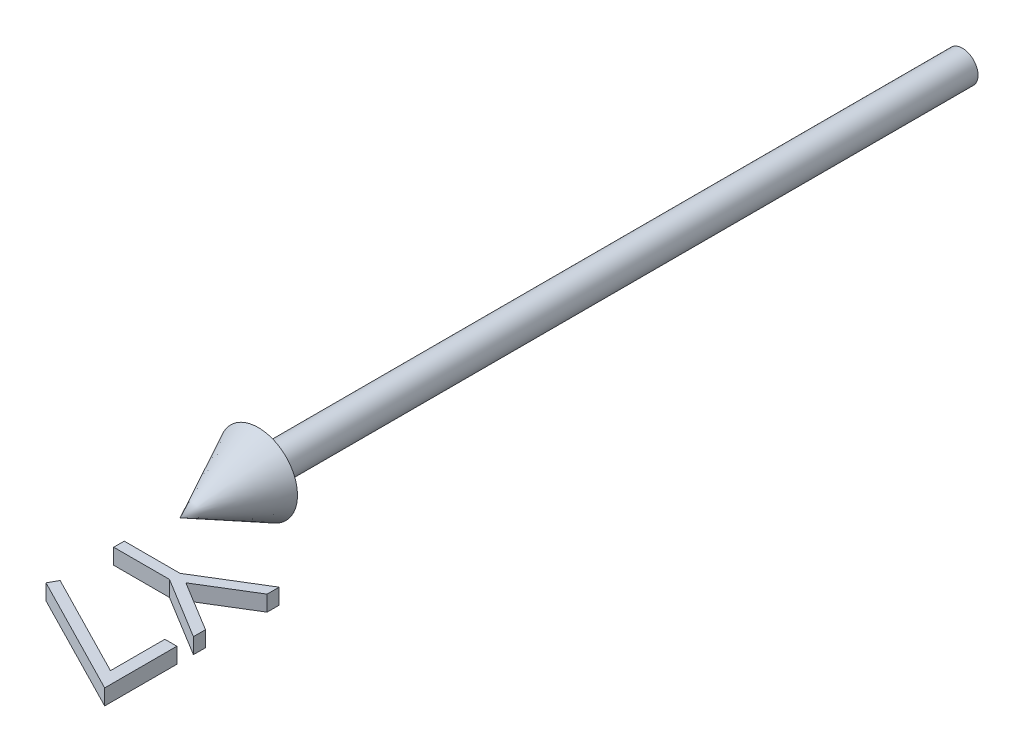
SolidWorks part; units mm, degrees
ref_plane "Front Plane" through (0, 0, 0) normal (0, 0, 1) x (1, 0, 0)
ref_plane "Top Plane" through (0, 0, 0) normal (0, 1, 0) x (1, 0, 0)
ref_plane "Right Plane" through (0, 0, 0) normal (1, 0, 0) x (0, 0, -1)
sketch "Sketch2" plane through (0, 0, 0) normal (0, 1, 0) x (1, 0, 0)
  line L0 (0, 41.95) -> (0, -114.4521) construction
  line L1 (-36.8894, 0) -> (41.4965, 0) construction
  line L2 (0, -100) -> (5, -90)
  line L3 (5, -90) -> (2, -90)
  line L4 (2, -90) -> (2, 0)
  line L5 (2, 0) -> (0, 0)
  line L6 (0, 0) -> (0, -100)
  dimension "D1" = 100
  dimension "D2" = 2
  dimension "D3" = 10
  dimension "D4" = 5
revolve "Revolve1" add sketch "Sketch2" angle 360 about L0
sketch "Sketch3" plane through (0, 0, 0) normal (0, 1, 0) x (1, 0, 0)
  line L0 (0, -101.5706) -> (0, -127.8138) construction
  text T0 "Y7\r\n\r\n\r\n" font "Century Gothic" height 15
extrude "Boss-Extrude1" add sketch "Sketch3" against normal blind 1 and the other way blind 1 separate body
equation "\"frame_arrow_length\"=100"
equation "\"D1@Sketch2\"=\"frame_arrow_length\""
equation "\"frame_arrow_odA\"=4"
equation "\"D2@Sketch2\"=\"frame_arrow_odA\"/2"
equation "\"frame_arrow_head_od\"=5"
equation "\"D4@Sketch2\"=\"frame_arrow_head_od\""
equation "\"frame_arrow_head_length\"=10"
equation "\"D3@Sketch2\"=\"frame_arrow_head_length\""
equation "\"tvarobot_theta1\"=30"
equation "\"link0_ringA_odA\"= 40"
equation "\"link0_ringA_odB\"= 25"
equation "\"link0_ringA_id\"= 20"
equation "\"link0_ringA_thickness\"= (\"link0_ringA_odB\" - \"link0_ringA_id\")/2"
equation "\"link0_ringA_height\"= 3"
equation "\"link0_ringA_heightA\"= 1.5"
equation "\"link0_ringA_heightB\"=\"link0_ringA_height\"-\"link0_ringA_heightA\""
equation "\"link0_ringB_odA\"= 40"
equation "\"link0_ringB_odB\"= 29"
equation "\"link0_ringB_id\"= \"link0_shaftA_bearing_id\"+1"
equation "\"link0_ringB_thickness\"= (\"link0_ringB_odB\" - \"link0_ringB_id\")/2"
equation "\"link0_ringB_height\"= 3"
equation "\"link0_ringB_heightA\"= 1.5"
equation "\"link0_ringB_heightB\"=\"link0_ringB_height\"-\"link0_ringB_heightA\""
equation "\"link0_shaftA_bearing_od\"=27"
equation "\"link0_shaftA_bearing_id\"=20"
equation "\"link0_shaftA_thrust_bearing_od\"=35"
equation "\"link0_shaftA_thrust_bearing_id\"=20.04"
equation "\"link0_shaftA_retaining_ring_id\"=18.5"
equation "\"link0_shaftA_retaining_ring_groove_width\"=1.5"
equation "\"link0_shaftA_spline_length\"=8.0"
equation "\"link0_shaftA_spline_depth\"=1.0"
equation "\"link0_shaftA_spline_width\"=4.0"
equation "\"link0_shaftA_odA\"=\"link0_shaftA_bearing_id\""
equation "\"link0_shaftA_odB\"=35"
equation "\"link0_shaftA_odC\"=\"link0_shaftA_bearing_id\""
equation "\"link0_shaftA_odD\"=\"link0_shaftA_odC\"-2*\"link0_shaftA_spline_depth\""
equation "\"link0_shaftA_odE\"=\"link0_shaftA_bearing_id\""
equation "\"link0_shaftA_odF\"=\"link0_shaftA_odE\"-2*\"link0_shaftA_spline_depth\""
equation "\"link0_shaftA_idA\"=10"
equation "\"link0_shaftA_idB\"=6"
equation "\"link0_shaftA_length\"=39.5"
equation "\"link0_shaftA_lengthA\"=8.0"
equation "\"link0_shaftA_lengthB\"=12.0"
equation "\"link0_shaftA_lengthC\"=35.0"
equation "\"link0_shaftA_lengthD\"=39.0"
equation "\"link0_shaftA_lengthE\"=\"link0_shaftA_length\"-\"link0_shaftA_lengthD\""
equation "\"link0_shaftA_offsetX\"=11"
equation "\"link0_shaftA_offsetY\"=0"
equation "\"link0_shaftA_bolt_pattern_dia\"=14"
equation "\"link0_motor_center_dist\"=26"
equation "\"link0_46t_pulley_spline_length\"=8"
equation "\"link0_46t_pulley_spline_depth\"=\"link0_shaftA_spline_depth\"*1.025"
equation "\"link0_46t_pulley_spline_width\"=\"link0_shaftA_spline_width\"*1.05"
equation "\"link0_46t_pulley_idA\"=\"link0_shaftA_bearing_id\"*1.025"
equation "\"link0_46t_pulley_idB\"=\"link0_46t_pulley_idA\"-2*\"link0_46t_pulley_spline_depth\""
equation "\"link0_shaftB_spline_length\"=10"
equation "\"link0_shaftB_spline_depth\"=1.0"
equation "\"link0_shaftB_spline_width\"=1.25"
equation "\"link0_shaftB_length\"=7"
equation "\"link0_shaftB_lengthA\"=1.5"
equation "\"link0_shaftB_lengthB\"=2.75"
equation "\"link0_shaftB_odA\"=32"
equation "\"link0_shaftB_odB\"=22"
equation "\"link0_shaftB_odC\"=20"
equation "\"link0_shaftB_idA\"=10"
equation "\"link0_shaftB_bolt_diameter\"=19"
equation "\"link0_shaftB_bearing_od\"=27"
equation "\"link0_shaftB_bearing_id\"=20"
equation "\"link0_motor_length\"=46.5"
equation "\"link0_motor_width\"=28.5"
equation "\"link0_motor_height\"=34"
equation "\"link0_motor_offset\"=8"
equation "\"link0_shellA_thickness\"=2.5"
equation "\"link0_shellB_thickness\"=\"link0_shellA_thickness\""
equation "\"link0_plateA_shellA_height\"=48"
equation "\"link0_shellA_width\" =\"link0_plateA_width\""
equation "\"link0_shellA_height\" = \"link0_plateA_shellA_height\"-\"link0_plateA_height\""
equation "\"link0_shellA_length\" = \"link0_plateA_lengthB\" "
equation "\"link0_shellB_length\"=\"link0_shellA_length\""
equation "\"link0_shellA_radius\" = 0.375*25.4"
equation "\"link0_shellA_radiusA\"= \"link0_plateA_radiusA\""
equation "\"link0_shellA_radiusB\"= \"link0_plateA_radiusB\""
equation "\"link0_shellA_radiusC\"= 3"
equation "\"link0_postA_height\"=7"
equation "\"link0_postA_width\"=16"
equation "\"link0_postA_length\"=20"
equation "\"link0_postA_posX\"=22"
equation "\"link0_postA_posY\"=17.5"
equation "\"link0_postA_pocket_width\"=6.0"
equation "\"link0_postA_pocket_length\"=2.5"
equation "\"link0_postA_pocket_depth\"=9"
equation "\"link0_postA_pocket_posZ\"=10"
equation "\"link0_postB_height\"=7"
equation "\"link0_postB_width\"=16"
equation "\"link0_postB_length\"=20"
equation "\"link0_postB_posX\"=22"
equation "\"link0_postB_posY\"=17.5"
equation "\"link0_postB_id\"=3.0"
equation "\"link0_postB_pocket_width\"=6.0"
equation "\"link0_postB_pocket_length\"=2.5"
equation "\"link0_postB_pocket_depth\"=9"
equation "\"link0_postB_pocket_posZ\"=10"
equation "\"link0_postC_height\"=7"
equation "\"link0_postC_width\"=16"
equation "\"link0_postC_length\"=20"
equation "\"link0_postC_posX\"=22"
equation "\"link0_postC_posY\"=17.5"
equation "\"link0_postC_id\"=3.0"
equation "\"link0_postC_pocket_width\"=6.0"
equation "\"link0_postC_pocket_length\"=2.5"
equation "\"link0_postC_pocket_depth\"=9"
equation "\"link0_postC_pocket_posZ\"=10"
equation "\"link0_postD_height\"=7"
equation "\"link0_postD_width\"=16"
equation "\"link0_postD_length\"=20"
equation "\"link0_postD_posX\"=22"
equation "\"link0_postD_posY\"=17.5"
equation "\"link0_postD_id\"=3.0"
equation "\"link0_postD_pocket_width\"=6.0"
equation "\"link0_postD_pocket_length\"=3.0"
equation "\"link0_postD_pocket_depth\"=9"
equation "\"link0_postD_pocket_posZ\"=10"
equation "\"link0_postE_height\"=5"
equation "\"link0_postE_width\"=16"
equation "\"link0_postE_length\"=\"link0_plateE_lengthA\"-\"link0_lip_height\""
equation "\"link0_postE_posZ\"=22"
equation "\"link0_postE_posX\"=17.5"
equation "\"link0_postE_posY\"=22"
equation "\"link0_postE_id\"=3.0"
equation "\"link0_postE_cbore_id\"=6.5"
equation "\"link0_postE_hole_id\"=3"
equation "\"link0_postF_posZ\"=22"
equation "\"link0_postF_posX\"=17.5"
equation "\"link0_postF_posY\"=\"link0_plateB_lengthA\"+4"
equation "\"link0_postF_id\"=3.0"
equation "\"link0_postF_cbore_id\"=6.5"
equation "\"link0_postF_hole_id\"=3"
equation "\"link0_postG_posZ\"=22"
equation "\"link0_postG_posX\"=17.5"
equation "\"link0_postG_posY\"=\"link0_plateB_lengthA\"+12"
equation "\"link0_postG_id\"=3.0"
equation "\"link0_postG_cbore_id\"=6.5"
equation "\"link0_postG_hole_id\"=3"
equation "\"link0_postHIJ_posY\"=6"
equation "\"link0_postH_posX\"=28"
equation "\"link0_postH_posY\"=20"
equation "\"link0_postH_posZ\"=20"
equation "\"link0_postH_length\"=10"
equation "\"link0_postI_posX\"=28"
equation "\"link0_postI_posY\"=20"
equation "\"link0_postI_posZ\"=135"
equation "\"link0_postI_length\"=10"
equation "\"link0_postJ_posX\"=28"
equation "\"link0_postJ_posY\"=20"
equation "\"link0_postJ_posZ\"=175"
equation "\"link0_postJ_length\"=10"
equation "\"link0_postK_posX\"=28"
equation "\"link0_postK_posY\"=20"
equation "\"link0_postK_posZ\"=175"
equation "\"link0_postK_length\"=10"
equation "\"link0_postL_posX\"=28"
equation "\"link0_postL_posY\"=20"
equation "\"link0_postL_posZ\"=135"
equation "\"link0_postL_length\"=10"
equation "\"link0_postM_posX\"=28"
equation "\"link0_postM_posY\"=20"
equation "\"link0_postM_posZ\"=35"
equation "\"link0_postM_length\"=10"
equation "\"link0_plateA_lengthA\"=30"
equation "\"link0_plateA_lengthB\"=150"
equation "\"link0_plateA_lengthC\"=30"
equation "\"link0_plateA_length\"=\"link0_plateA_lengthA\"+\"link0_plateA_lengthB\"+\"link0_plateA_lengthC\""
equation "\"link0_plateA_width\"=  68"
equation "\"link0_plateA_height\"= \"link0_plateA_radiusA\""
equation "\"link0_plateA_thickness\"=\"link0_shellA_thickness\""
equation "\"link0_plateA_radius\"= 9.5"
equation "\"link0_plateA_radiusA\"= 18"
equation "\"link0_plateA_radiusB\"= 18"
equation "\"link0_plateA_radiusC\"= 3"
equation "\"link0_plateB_length\"= 40"
equation "\"link0_plateB_width\"= \"link0_plateA_width\"*1.005"
equation "\"link0_plateB_height\"= \"link0_plateA_shellA_height\"*1.005"
equation "\"link0_plateB_lengthA\"=\"link0_lip_height\"+\"link0_plateD_thickness\"+\"link0_motor_mount_thickness\""
equation "\"link0_plateB_lengthB\"=\"link0_plateB_height\"-\"link0_plateB_lengthA\""
equation "\"link0_plateB_radiusA\"= \"link0_plateA_radiusA\""
equation "\"link0_plateB_radiusB\"= \"link0_plateA_radiusB\""
equation "\"link0_plateB_radiusC\"= 3"
equation "\"link0_plateB_idA\"=\"link0_shaftA_odC\"+1"
equation "\"link0_plateB_idB\"=\"link0_shaftA_bearing_od\"-2"
equation "\"link0_plateB_idC\"=\"link0_shaftA_bearing_od\"*1.005"
equation "\"link0_plateB_idD\"=\"link0_shaftA_thrust_bearing_od\"+1 "
equation "\"link0_plateB_depthA\"=1.0"
equation "\"link0_plateB_depthB\"=2.0"
equation "\"link0_plateB_depthC\"=8"
equation "\"link0_plateB_depthD\"=\"link0_plateB_length\"-\"link0_lip_height\"-\"link0_plateD_thickness\" "
equation "\"link0_plateC_length\"=\"link0_plateB_length\""
equation "\"link0_plateC_width\"= \"link0_plateB_width\""
equation "\"link0_plateC_height\"= .1*25.4"
equation "\"link0_plateA_hole_od\" = 0.1*25.4"
equation "\"link0_plateA_hole_delx\" = 0.5*25.4"
equation "\"link0_plateA_hole_delz\" = 0.75*25.4"
equation "\"link0_plateA_hole_offx\" = 0.0*25.4"
equation "\"link0_plateA_hole_offz\" = \"link0_plateA_length\"/2"
equation "\"link0_plateB_hole_od\" = 0.1*25.4"
equation "\"link0_plateB_hole_delx\"= 0.75*25.4"
equation "\"link0_plateB_hole_delz\"= 0.75*25.4"
equation "\"link0_plateB_hole_offx\"= 0.0*25.4"
equation "\"link0_plateB_hole_offz\"= 0.0*25.4"
equation "\"link0_plateC_hole_od\"= 0.1*25.4"
equation "\"link0_plateC_hole_delx\"= 0.75*25.4"
equation "\"link0_plateC_hole_delz\"= 0.75*25.4"
equation "\"link0_plateC_hole_offx\"= 0.0*25.4"
equation "\"link0_plateC_hole_offz\"= 0.0*25.4"
equation "\"link0_plateD_height\"=\"link0_plateB_height\"-2*\"link0_shellA_thickness\""
equation "\"link0_plateD_width\"=\"link0_plateB_width\"-2*\"link0_shellA_thickness\""
equation "\"link0_plateD_thickness\"=10"
equation "\"link0_plateD_radiusA\"=\"link0_plateB_radiusA\"-\"link0_shellA_thickness\""
equation "\"link0_plateD_odA\"= .375*25.4"
equation "\"link0_plateD_odB\"= .375*25.4"
equation "\"link0_plateD_bearing_id\"=20"
equation "\"link0_plateD_bearing_od\"=27"
equation "\"link0_plateE_radiusA\"=\"link0_plateA_radiusA\""
equation "\"link0_plateE_radiusB\"=\"link0_plateA_radiusB\""
equation "\"link0_plateE_radiusC\"=8.0"
equation "\"link0_plateE_length\"=30"
equation "\"link0_plateE_lengthA\"=16"
equation "\"link0_plateE_height\"=\"link0_plateB_height\""
equation "\"link0_plateE_width\"=\"link0_plateB_width\""
equation "\"link0_plateE_odA\"=\"gantry_coupler_id\"*0.99"
equation "\"link0_plateE_idA\"=\"link0_plateE_odA\"-20.0"
equation "\"link0_plateE_spline_depth\"=\"link0_poleA_spline_depth\"*1.05"
equation "\"link0_plateE_spline_width\"=\"link0_poleA_spline_width\"*1.075"
equation "\"link0_plateE_spline_length\"=\"link0_poleA_spline_length\""
equation "\"link0_plateE_coupler_length\"=46"
equation "\"link0_lip_height\"=5.0"
equation "\"link0_lip_thickness\"=2.0"
equation "\"link0_motor_mount_thickness\"=8.0"
equation "\"link0_motor_mount_idA\"=22"
equation "\"link0_motor_mount_idB\"=\"link0_shaftB_bearing_od\"*1.005"
equation "\"link0_motor_mount_idC\"=\"link0_shaftB_bearing_od\"-2"
equation "\"link0_motor_mount_depthA\"=5.5"
equation "\"link0_motor_mount_height\"=\"link0_plateD_height\""
equation "\"link0_motor_mount_width\"=\"link0_plateD_width\""
equation "\"link0_motor_mountL_height\"=36"
equation "\"link0_motor_mountL_heightA\"=12"
equation "\"link0_motor_mountL_length\"=50"
equation "\"link0_motor_mountL_lengthA\"=36"
equation "\"gantry_coupler_od\"=25.4*2.0"
equation "\"gantry_coupler_id\"=1.645*25.4"
equation "\"gantry_coupler_offsetX\"=\"link0_plateE_width\"/2"
equation "\"link0_poleA_odA\"=20"
equation "\"link0_poleA_odB\"=36"
equation "\"link0_poleA_idA\"=\"link0_poleA_odA\"-2*\"link0_poleA_thickness\""
equation "\"link0_poleA_idB\"=(\"link0_plateE_idA\"/2+1.5*\"link0_lip_thickness\")*1.04"
equation "\"link0_poleA_thickness\"=3.5"
equation "\"link0_poleA_length\"=100"
equation "\"link0_poleA_lengthA\"=18.5"
equation "\"link0_poleA_lengthB\"=80"
equation "\"link0_poleA_gasket_thickness\"=1.5"
equation "\"link0_poleA_spline_depth\"=1.0"
equation "\"link0_poleA_spline_width\"=4.0"
equation "\"link0_poleA_spline_length\"=10.0"
equation "\"link1_plateB_length\"=30"
equation "\"link1_lip_height\"=\"link0_lip_height\""
equation "\"link0_tension_plateA_width\"=12"
equation "\"link0_tension_plateA_lengthA\"=10.5"
equation "\"link0_tension_plateB_width\"=\"link0_tension_plateA_width\""
equation "\"link0_tension_plateB_lengthA\"=\"link0_tension_plateA_lengthA\""
equation "\"link0_tension_wheelA_posZ\"=7"
equation "\"link0_tension_wheelA_posX\"=\"link0_plateD_height\"/2-\"link0_tension_plateA_lengthA\""
equation "\"link0_m2_clear_hole_id\"=2.35"
equation "\"link0_m2_insert_hole_id\"=2.5"
equation "\"link0_m2_tap_hole_id\"=1.75"
equation "\"link0_m2_nut_socket_width\"=4.25"
equation "\"link0_m2_nut_socket_depth\"=2.5"
equation "\"link0_m2_cbore_id\"=3.75"
equation "\"link0_m2_cbore_depth\"=7"
equation "\"link0_m2_5_clear_hole_id\"=2.75"
equation "\"link0_m2_5_insert_hole_id\"=2.75"
equation "\"link0_m2_5_tap_hole_id\"=2.25"
equation "\"link0_m2_5_nut_socket_width\"=5.25"
equation "\"link0_m2_5_nut_socket_depth\"=2.5"
equation "\"link0_m2_5_cbore_id\"=4.75"
equation "\"link0_m2_5_cbore_depth\"=2.5"
equation "\"link0_m2_5_insert_access_length\"=6.0"
equation "\"link0_m2_5_insert_access_width\"=3.0"
equation "\"link0_m3_clear_hole_id\"=3.25"
equation "\"link0_m3_insert_hole_id\"=3"
equation "\"link0_m3_tap_hole_id\"=2.75"
equation "\"link0_m3_nut_socket_width\"=5.75"
equation "\"link0_m3_nut_socket_depth\"=4.0"
equation "\"link0_m3_cbore_id\"=5.75"
equation "\"link0_m3_cbore_depth\"=3.5"
equation "\"link0_m3_insert_access_length\"=4.5"
equation "\"link0_m3_insert_access_width\"=3.5"
equation "\"link0_rpi_mount_height\"=6"
equation "\"link0_rpi_mount_width\"=49"
equation "\"link0_rpi_mount_length\"=58"
equation "\"link0_rpi_mount_post_od\"=6"
equation "\"link0_rpi_mount_posZ\"=72"
equation "\"link0_rpi_mount_posX\"=11.5"
equation "\"link0_mcu_mount_height\"=5"
equation "\"link0_mcu_mount_width\"=49"
equation "\"link0_mcu_mount_length\"=58"
equation "\"link0_mcu_mount_post_od\"=6"
equation "\"link0_mcu_mount_posZ\"=164"
equation "\"link0_mcu_mount_posX\"=4"
equation "\"link0_pwr_mount_height\"=4"
equation "\"link0_pwr_mount_width\"=15.75"
equation "\"link0_pwr_mount_length\"=75.75"
equation "\"link0_pwr_mount_post_od\"=6"
equation "\"link0_pwr_mount_posZ\"=75"
equation "\"link0_pwr_mount_posX\"=16"
equation "\"link0_pwr_board_height\"=6"
equation "\"link0_pwr_board_width\"=21"
equation "\"link0_pwr_board_length\"=80"
